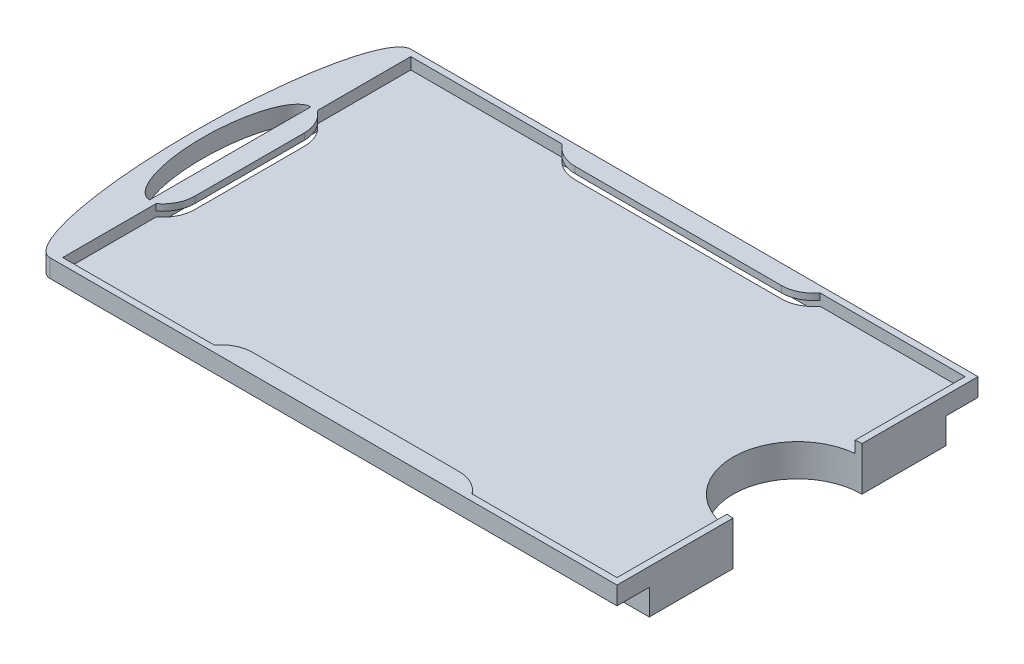
SolidWorks part; units mm, degrees
ref_plane "Front" through (0, 0, 0) normal (0, 0, 1) x (1, 0, 0)
ref_plane "Top" through (0, 0, 0) normal (0, 1, 0) x (1, 0, 0)
ref_plane "Right" through (0, 0, 0) normal (1, 0, 0) x (0, 0, -1)
sketch "Çizim1" plane through (0, 0, 0) normal (0, 1, 0) x (1, 0, 0)
  line L1 (-46.1164, 15.8979) -> (41.8836, 15.8979)
  line L2 (-46.1164, 15.8979) -> (-46.1164, -40.1021)
  line L3 (-46.1164, -40.1021) -> (41.8836, -40.1021)
  line L4 (41.8836, 15.8979) -> (41.8836, -40.1021)
  dimension "D1" = 88
  dimension "D2" = 56
extrude "Yükseklik-Ekstrüzyon1" add sketch "Çizim1" along normal blind 2.8 contours L4 L3 L2 L1
shell "İç Boşaltma1" thickness 1 removed face at (-2.1164, 2.8, 12.1021)
sketch "Çizim3" plane through (0, 2.8, 0) normal (0, 1, 0) x (1, 0, 0)
  line L0 (41.8836, 15.8979) -> (41.8836, -40.1021) construction
  circle A0 centre (41.8836, -12.1021) radius 10
  dimension "D1" = 20
extrude "Kes-Ekstrüzyon2" cut sketch "Çizim3" against normal blind 30.7
sketch "Çizim4" plane through (0, 2.8, 0) normal (0, 1, 0) x (1, 0, 0)
  line L0 (-46.1164, 15.8979) -> (-46.1164, -40.1021) construction
  line L1 (-21.6164, 12.8979) -> (-21.6164, 15.8979)
  line L2 (-46.1164, 15.8979) -> (41.8836, 15.8979) construction
  line L3 (18.3836, 12.8979) -> (-21.6164, 12.8979)
  line L4 (18.3836, 12.8979) -> (18.3836, 15.8979)
  line L7 (40.8836, -2.1522) -> (40.8836, 14.8979) construction
  line L8 (-21.6164, -40.1021) -> (18.3836, -40.1021)
  line L9 (18.3836, -37.1021) -> (18.3836, -40.1021)
  line L10 (18.3836, -37.1021) -> (-21.6164, -37.1021)
  line L11 (-21.6164, 15.8979) -> (18.3836, 15.8979)
  line L12 (-21.6164, -37.1021) -> (-21.6164, -40.1021)
  line L14 (-46.1164, 0.3979) -> (-43.1164, 0.3979)
  line L15 (-46.1164, 0.3979) -> (-46.1164, -24.6021)
  line L16 (-46.1164, -24.6021) -> (-43.1164, -24.6021)
  line L17 (-43.1164, 0.3979) -> (-43.1164, -24.6021)
  dimension "D1" = 3
  dimension "D2" = 40
  dimension "D3" = 22.5
  dimension "D4" = 25
  dimension "D5" = 15.5
  dimension "D6" = 3
extrude "Yükseklik-Ekstrüzyon2" add sketch "Çizim4" against normal blind 1
fillet "Radyus1" radius 5 6 edges at (18.3836, 2.3, -12.8979) (-21.6164, 2.3, -12.8979) (-21.6164, 2.3, 37.1021) (18.3836, 2.3, 37.1021) (-43.1164, 2.3, 24.6021) (-43.1164, 2.3, -0.3979)
sketch "Çizim5" plane through (0, 1.8, 0) normal (0, -1, 0) x (-1, 0, 0)
  line L0 (21.6164, 14.8979) -> (-18.3836, 14.8979) construction
  line L1 (-14.3836, 12.8979) -> (17.6164, 12.8979) construction
  line L2 (-18.3836, -39.1021) -> (21.6164, -39.1021) construction
  line L3 (17.6164, -37.1021) -> (-14.3836, -37.1021) construction
  line L4 (21.6164, 14.8979) -> (-18.3836, 14.8979)
  line L5 (-14.3836, 12.8979) -> (17.6164, 12.8979)
  line L6 (-18.3836, -39.1021) -> (21.6164, -39.1021)
  line L7 (17.6164, -37.1021) -> (-14.3836, -37.1021)
  line L10 (43.1164, -3.6021) -> (43.1164, -20.6021)
  line L11 (45.1164, -24.6021) -> (45.1164, 0.3979)
  line L12 (43.1164, -3.6021) -> (43.1164, -20.6021)
  line L13 (45.1164, -24.6021) -> (45.1164, 0.3979)
  arc A0 (-18.3836, 14.8979) -> (-14.3836, 12.8979) centre (-14.3836, 17.8979) ccw construction
  arc A1 (17.6164, 12.8979) -> (21.6164, 14.8979) centre (17.6164, 17.8979) ccw construction
  arc A2 (21.6164, -39.1021) -> (17.6164, -37.1021) centre (17.6164, -42.1021) ccw construction
  arc A3 (-14.3836, -37.1021) -> (-18.3836, -39.1021) centre (-14.3836, -42.1021) ccw construction
  arc A4 (-18.3836, 14.8979) -> (-14.3836, 12.8979) centre (-14.3836, 17.8979) ccw
  arc A5 (17.6164, 12.8979) -> (21.6164, 14.8979) centre (17.6164, 17.8979) ccw
  arc A6 (21.6164, -39.1021) -> (17.6164, -37.1021) centre (17.6164, -42.1021) ccw
  arc A7 (-14.3836, -37.1021) -> (-18.3836, -39.1021) centre (-14.3836, -42.1021) ccw
  arc A10 (43.1164, -20.6021) -> (45.1164, -24.6021) centre (48.1164, -20.6021) ccw
  arc A11 (45.1164, 0.3979) -> (43.1164, -3.6021) centre (48.1164, -3.6021) ccw
  arc A12 (43.1164, -20.6021) -> (45.1164, -24.6021) centre (48.1164, -20.6021) ccw
  arc A13 (45.1164, 0.3979) -> (43.1164, -3.6021) centre (48.1164, -3.6021) ccw
  dimension "D1" = 0
extrude "Kes-Ekstrüzyon3" cut sketch "Çizim5" along normal blind 31
sketch "Çizim6" plane through (0, 0, 0) normal (0, -1, 0) x (1, 0, 0)
  line L0 (14.5835, 36.1021) -> (-17.6164, 36.1021)
  line L1 (14.3836, 37.1021) -> (-17.6164, 37.1021) construction
  line L2 (-17.6164, -12.8979) -> (14.3836, -12.8979) construction
  line L3 (-43.1164, 20.6021) -> (-43.1164, 3.6021) construction
  line L4 (14.3836, 37.1021) -> (-17.6164, 37.1021)
  line L5 (-17.6164, -12.8979) -> (14.3836, -12.8979)
  line L6 (-43.1164, 20.6021) -> (-43.1164, 3.6021)
  line L7 (-21.6164, 39.1021) -> (-21.6164, 40.1021)
  line L8 (-46.1164, 40.1021) -> (41.8836, 40.1021) construction
  line L9 (-21.6164, 40.1021) -> (-46.1164, 40.1021)
  line L10 (-46.1164, 40.1021) -> (-46.1164, 24.6021)
  line L11 (-46.1164, -15.8979) -> (-46.1164, 40.1021) construction
  line L12 (-46.1164, 24.6021) -> (-45.1164, 24.6021)
  line L13 (18.3836, 39.1021) -> (18.3836, 40.1021)
  line L14 (18.3836, 40.1021) -> (41.8836, 40.1021)
  line L15 (41.8836, 22.1021) -> (41.8836, 40.1021)
  line L16 (41.8836, 2.1021) -> (41.8836, -15.8979)
  line L17 (-17.6164, -11.8979) -> (14.3836, -11.8979)
  line L18 (41.8836, -15.8979) -> (18.3836, -15.8979)
  line L19 (-46.1164, -15.8979) -> (41.8836, -15.8979) construction
  line L20 (18.3836, -15.8979) -> (18.3836, -14.8979)
  line L21 (-21.6164, -14.8979) -> (-21.6164, -15.8979)
  line L22 (-21.6164, -15.8979) -> (-46.1164, -15.8979)
  line L23 (-46.1164, -15.8979) -> (-46.1164, -0.3979)
  line L24 (-46.1164, -0.3979) -> (-45.1164, -0.3979)
  line L25 (-42.1164, 20.6021) -> (-42.1164, 3.6021)
  line L26 (-42.1164, 20.6021) -> (-42.1164, 36.1021)
  line L27 (14.3836, -11.8979) -> (40.8836, -11.8979)
  line L28 (-42.1164, 3.6021) -> (-42.1164, -11.8979)
  line L32 (40.8836, 23.0566) -> (40.8836, 36.1021)
  line L33 (40.8836, 1.1477) -> (40.8836, -11.8979)
  line L34 (14.5835, 36.1021) -> (40.8836, 36.1021)
  line L37 (-17.6164, 36.1021) -> (-42.1164, 36.1021)
  line L40 (-17.6164, -11.8979) -> (-42.1164, -11.8979)
  arc A0 (14.3836, 37.1021) -> (18.3836, 39.1021) centre (14.3836, 42.1021) ccw construction
  arc A1 (-21.6164, 39.1021) -> (-17.6164, 37.1021) centre (-17.6164, 42.1021) ccw construction
  arc A2 (41.8836, 22.1021) -> (41.8836, 2.1021) centre (41.8836, 12.1021) ccw construction
  arc A4 (-17.6164, -12.8979) -> (-21.6164, -14.8979) centre (-17.6164, -17.8979) ccw construction
  arc A5 (-45.1164, -0.3979) -> (-43.1164, 3.6021) centre (-48.1164, 3.6021) ccw construction
  arc A6 (-43.1164, 20.6021) -> (-45.1164, 24.6021) centre (-48.1164, 20.6021) ccw construction
  arc A7 (14.3836, 37.1021) -> (18.3836, 39.1021) centre (14.3836, 42.1021) ccw
  arc A8 (-21.6164, 39.1021) -> (-17.6164, 37.1021) centre (-17.6164, 42.1021) ccw
  arc A9 (41.8836, 22.1021) -> (41.8836, 2.1021) centre (41.8836, 12.1021) ccw
  arc A12 (18.3836, -14.8979) -> (14.3836, -12.8979) centre (13.8936, -18.8778) ccw
  arc A13 (-17.6164, -12.8979) -> (-21.6164, -14.8979) centre (-17.6164, -17.8979) ccw
  arc A14 (-45.1164, -0.3979) -> (-43.1164, 3.6021) centre (-48.1164, 3.6021) ccw
  arc A15 (-43.1164, 20.6021) -> (-45.1164, 24.6021) centre (-48.1164, 20.6021) ccw
  arc A16 (40.8836, 23.0566) -> (40.8836, 1.1477) centre (41.8836, 12.1021) ccw
  dimension "D11" = 1
  dimension "D17" = 0
  dimension "D18" = 11
  dimension "D23" = 1
  dimension "D5" = 1
  dimension "D16" = 1
  dimension "D19" = 1
extrude "Yükseklik-Ekstrüzyon3" [suppressed] add sketch "Çizim6" along normal blind 6
sketch "Çizim8" plane through (0, 0, 0) normal (0, -1, 0) x (1, 0, 0)
  line L0 (41.8836, 35.1021) -> (-41.1164, 35.1021)
  line L1 (39.8836, 23.9343) -> (39.8836, 33.1021)
  line L2 (-17.8779, 33.1021) -> (-39.1164, 33.1021)
  line L3 (14.3219, 33.1021) -> (39.8836, 33.1021)
  line L4 (-17.6164, -8.8979) -> (-39.1164, -8.8979)
  line L5 (14.3836, -8.8979) -> (39.8836, -8.8979)
  line L6 (-39.1164, 21.4029) -> (-39.1164, 33.1021)
  line L7 (-39.1164, 4.3697) -> (-39.1164, -8.8979)
  line L8 (-41.1164, 35.1021) -> (-41.1164, -10.8979)
  line L9 (-41.1164, -10.8979) -> (41.8836, -10.8979)
  line L10 (41.8836, 22.1021) -> (41.8836, 40.1021) construction
  line L12 (41.8836, 22.1021) -> (41.8836, 40.1021)
  line L13 (41.8836, 22.1021) -> (41.8836, 40.1021)
  line L14 (41.8836, 40.1021) -> (-46.1164, 40.1021)
  line L15 (41.8836, 40.1021) -> (-46.1164, 40.1021)
  line L16 (-46.1164, 40.1021) -> (-46.1164, -15.8979)
  line L17 (-46.1164, 40.1021) -> (-46.1164, -15.8979)
  line L18 (-46.1164, -15.8979) -> (41.8836, -15.8979)
  line L19 (-46.1164, -15.8979) -> (41.8836, -15.8979)
  line L20 (41.8836, -15.8979) -> (41.8836, 2.1021)
  line L21 (41.8836, -15.8979) -> (41.8836, 2.1021)
  line L37 (14.3219, 33.1021) -> (-17.8779, 33.1021)
  line L42 (-39.1164, 21.4029) -> (-39.1164, 4.3697)
  line L47 (-17.6164, -8.8979) -> (14.3836, -8.8979)
  line L50 (39.8836, -8.8979) -> (39.8836, 0.27)
  arc A1 (41.8836, 22.1021) -> (41.8836, 2.1021) centre (41.8836, 12.1021) ccw
  arc A2 (41.8836, 22.1021) -> (41.8836, 2.1021) centre (41.8836, 12.1021) ccw
  arc A6 (39.8836, 23.9343) -> (39.8836, 0.27) centre (41.8836, 12.1021) ccw
  point P8 (41.8836, 36.915)
  point P17 (41.8836, 12.5063)
  dimension "D6" = 5
  dimension "D8" = 5
  dimension "D13" = 12
  dimension "D2" = 0
  dimension "D3" = 2
  dimension "D4" = 2
  dimension "D5" = 2
  dimension "D7" = 5
extrude "Yükseklik-Ekstrüzyon5" add sketch "Çizim8" along normal blind 4 contours L1 A6 L50 L47 L42 L37 region at (40.9347, 0, 28.6021)
sketch "Çizim7" plane through (0, 0, 0) normal (0, -1, 0) x (1, 0, 0)
  circle A0 centre (-18.2501, 0.9196) radius 0.75
  circle A1 centre (-19.2001, 24.214) radius 0.75
  point P5 (0, 0)
  point P6 (-26.6249, 24.2028)
  point P7 (-25.6749, 0.9084)
  dimension "D1" = 1.5
  dimension "D2" = 1.5
  dimension "D3" = 0.95
  dimension "D4" = 23.2944
extrude "Yükseklik-Ekstrüzyon4" add sketch "Çizim7" along normal up to surface (4 mm away) up to face at (12.5503, -4, 12.1021)
sketch "Çizim11" plane through (0, 0, -10.8979) normal (0, 0, -1) x (-1, 0, 0)
  line L1 (17.6164, 0) -> (-14.3836, 0) construction
  line L2 (-41.8836, -4) -> (41.1164, -4) construction
  circle A0 centre (1.6164, -2) radius 1
  point P4 (1.6164, 0)
  dimension "D1" = 2
  dimension "D2" = 0
extrude "Kes-Ekstrüzyon4" cut sketch "Çizim11" against normal blind 100
sketch "Çizim12" plane through (0, 2.8, 0) normal (0, 1, 0) x (1, 0, 0)
  line L0 (-46.1164, 15.8979) -> (-46.1164, -40.1021) construction
  line L1 (-46.1164, -40.1021) -> (-46.1164, 15.8979)
  ellipse E0 centre (-46.1164, -12.1021) end of major axis (-46.1164, 0.3979) minor radius 4.2638 (-46.1164, 0.3979) -> (-46.1164, -24.6021) ccw
  ellipse E1 centre (-46.1164, -12.1021) end of major axis (-46.1164, 15.8979) minor radius 5.7691 (-46.1164, 15.8979) -> (-46.1164, -40.1021) ccw
  line M15 (-46.1164, 15.8979) -> (-46.1164, -40.1021)
extrude "Yükseklik-Ekstrüzyon6" add sketch "Çizim12" against normal up to surface (2.8 mm away) contours E1 E0 M15 region at (-51.3225, 2.8, 12.1021) up to face at (-0.8664, 0, 12.1021)
